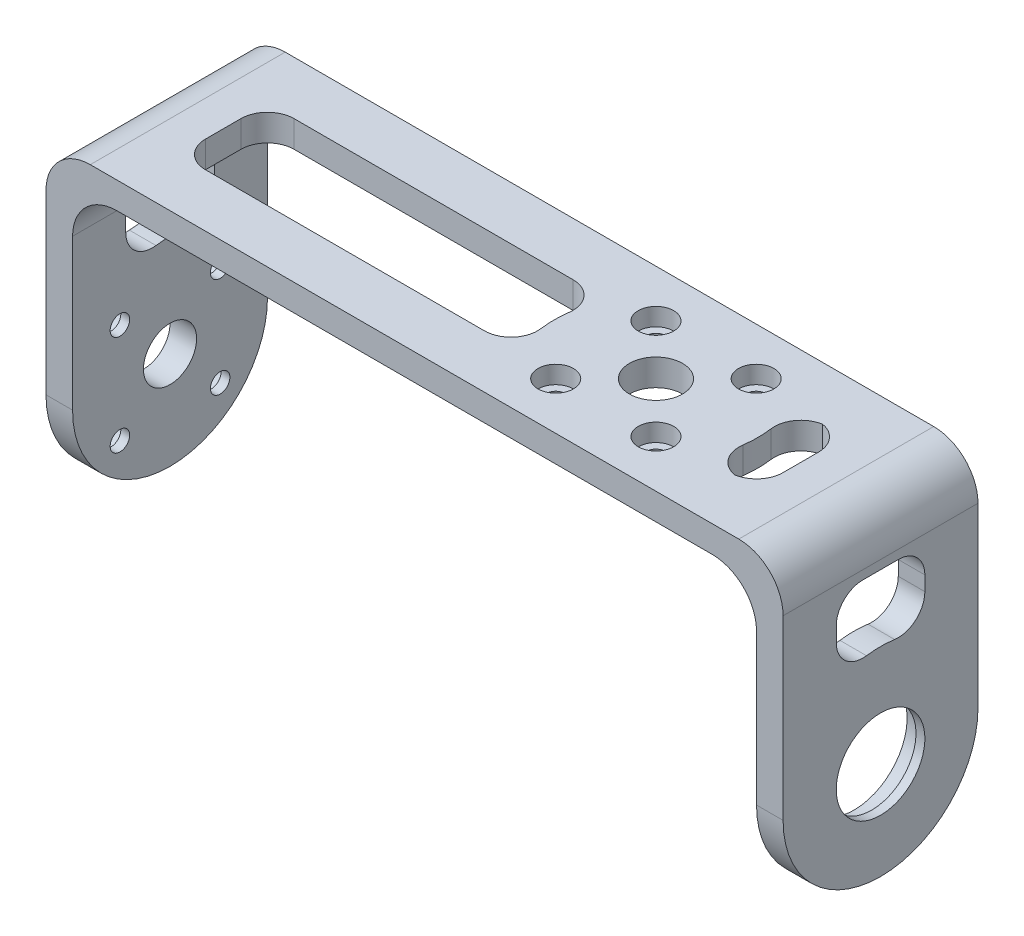
SolidWorks part; units mm, degrees
ref_plane "Front Plane" through (0, 0, 0) normal (0, 0, 1) x (1, 0, 0)
ref_plane "Top Plane" through (0, 0, 0) normal (0, 1, 0) x (1, 0, 0)
ref_plane "Right Plane" through (0, 0, 0) normal (1, 0, 0) x (0, 0, -1)
sketch "Sketch1" plane through (0, 0, 0) normal (0, 1, 0) x (1, 0, 0)
  line L0 (16.25, 0) -> (18.3713, 2.1213) construction
  line L1 (38.6, 11) -> (-38.6, 11)
  line L2 (38.6, 11) -> (38.6, -11)
  line L3 (38.6, -11) -> (-38.6, -11)
  line L4 (-38.6, 11) -> (-38.6, -11)
  line L5 (38.6, 11) -> (-38.6, -11) construction
  line L6 (38.6, -11) -> (-38.6, 11) construction
  line L7 (-38.6, 11) -> (-41.6, 11)
  line L8 (-38.6, 11) -> (-38.6, -11)
  line L9 (-38.6, -11) -> (-41.6, -11)
  line L10 (-41.6, 11) -> (-41.6, -11)
  line L11 (38.6, 11) -> (41.6, 11)
  line L12 (38.6, 11) -> (38.6, -11)
  line L13 (38.6, -11) -> (41.6, -11)
  line L14 (41.6, 11) -> (41.6, -11)
  line L15 (-32.6, 5) -> (-32.6, 11) construction
  line L16 (32.6, 5) -> (26.6062, 5)
  line L17 (32.6, 5) -> (32.6, -5)
  line L18 (32.6, -5) -> (26.6062, -5)
  line L19 (-32.6, 5) -> (-32.6, -5)
  line L20 (32.6, 5) -> (-32.6, -5) construction
  line L21 (32.6, -5) -> (-32.6, 5) construction
  line L22 (-32.6, 5) -> (-38.6, 5) construction
  line L23 (5.8938, 5) -> (-32.6, 5)
  line L24 (5.8938, -5) -> (-32.6, -5)
  circle A0 centre (16.25, 0) radius 3
  arc A1 (5.8938, 5) -> (5.8938, -5) centre (16.25, 0) ccw
  arc A2 (26.6062, -5) -> (26.6062, 5) centre (16.25, 0) ccw
  point P0 (0, 0)
  point P13 (0, 0)
  dimension "D5" = 6
  dimension "D8" = 23
  dimension "D1" = 77.2
  dimension "D2" = 22
  dimension "D3" = 3
  dimension "D4" = 22.35
  dimension "D6" = 45
  dimension "D7" = 6
extrude "Boss-Extrude1" add sketch "Sketch1" against normal blind 3 contours L1 L4 L3 L2 region at (37.7973, 0, 0)
extrude "Boss-Extrude2" add sketch "Sketch1<3>" against normal blind 36 separate body contours L7 L10 L9 L4 | L14 L11 L2 L13 region at (40.1, 0, 0) region at (-40.1, 0, 0)
sketch "Sketch1<3>" plane through (0, 0, 0) normal (0, 1, 0) x (1, 0, 0) same geometry as "Sketch1"
sketch "Sketch2" plane through (-41.6, 0, 0) normal (-1, 0, 0) x (0, 0, 1)
  line L0 (0, -25) -> (5.6569, -19.3431) construction
  line L3 (-11, -36) -> (11, -36) construction
  circle A0 centre (0, -25) radius 3
  circle A1 centre (5.6569, -19.3431) radius 1.1
  dimension "D1" = 6
  dimension "D5" = 2.2
  dimension "D2" = 11
  dimension "D3" = 8
  dimension "D4" = 45
extrude "Cut-Extrude1" cut sketch "Sketch2" against normal up to surface (3 mm away) contours A0 | A1 region at (-41.6, -25, 0) up to face at (-38.6, -18, 0)
sketch "Sketch4" plane through (0, 0, 0) normal (0, 1, 0) x (1, 0, 0)
  line L0 (21.9069, 5.6569) -> (16.25, 0) construction
  line L1 (38.6, 11) -> (-38.6, 11) construction
  circle A0 centre (21.9069, 5.6569) radius 1.1
  dimension "D3" = 2.2
  dimension "D1" = 45
  dimension "D2" = 8
extrude "Cut-Extrude3" cut sketch "Sketch4" against normal up to surface (3 mm away) up to face at (16.25, -3, 3)
pattern_circular "CirPattern2" count 4 over 360 about axis through (16.25, 0, 0) along (0, 1, 0) of "Cut-Extrude3"
sketch "Sketch5" plane through (-41.6, 0, 0) normal (-1, 0, 0) x (0, 0, 1)
  line L0 (-11, -6) -> (-5, -6) construction
  line L2 (-5, -14.6438) -> (-5, -6)
  line L3 (-5, -6) -> (5, -6)
  line L4 (5, -14.6438) -> (5, -6)
  line L5 (-11, -36) -> (-11, 0) construction
  line L6 (-5, -6) -> (-5, 0) construction
  line L7 (55, 0) -> (-55, 0) construction
  line L8 (5, -6) -> (11, -6) construction
  line L9 (11, -36) -> (11, 0) construction
  arc A0 (5, -14.6438) -> (-5, -14.6438) centre (0, -25) ccw
  circle A1 centre (0, -25) radius 3 construction
  dimension "D2" = 23
  dimension "D1" = 6
extrude "Cut-Extrude4" cut sketch "Sketch5" against normal up to surface (83.2 mm away) up to face at (41.6, -18, 0)
sketch "Sketch6" plane through (38.6, 0, 0) normal (-1, 0, 0) x (0, 0, 1)
  circle A0 centre (0, -25) radius 6
  circle A1 centre (0, -25) radius 3 construction
  circle A2 centre (0, -25) radius 5
  dimension "D1" = 12
  dimension "D2" = 10
extrude "Cut-Extrude5" cut sketch "Sketch6" against normal offset from surface (2 mm away) 1 contours A2 | A0 A2 region at (38.6, -25, -5.8303) region at (38.6, -25, 0) up to face at (41.6, -10.036, 0)
extrude "Cut-Extrude6" cut sketch "Sketch6<3>" against normal up to surface (3 mm away) contours A2 region at (38.6, -25, 0) up to face at (41.6, -10.036, 0)
sketch "Sketch6<3>" plane through (38.6, 0, 0) normal (-1, 0, 0) x (0, 0, 1) same geometry as "Sketch6"
combine bodies "Combine1" operation type add bodies to combine 110 108 112
fillet "Fillet2" radius 5 4 edges at (41.6, 0, 0) (-41.6, 0, 0) (38.6, -3, 0) (-38.6, -3, 0)
pattern_circular "CirPattern3" count 4 over 360 about axis through (-30.1147, -25, 0) along (-1, 0, 0) of "Cut-Extrude1" reverse direction yes
fillet "Fillet3" radius 11 4 edges at (40.1, -36, 11) (40.1, -36, -11) (-40.1, -36, -11) (-40.1, -36, 11)
fillet "Fillet4" radius 3 16 edges at (40.1, -14.6438, -5) (40.1, -14.6438, 5) (39.8913, -6, 5) (39.8913, -6, -5) (32.6, -1.5, 5) (26.6062, -1.5, 5) (26.6062, -1.5, -5) (32.6, -1.5, -5) (5.8938, -1.5, 5) (-32.6, -1.5, 5) (-32.6, -1.5, -5) (5.8938, -1.5, -5) (-39.8913, -6, -5) (-39.8913, -6, 5) (-40.1, -14.6438, 5) (-40.1, -14.6438, -5)
sketch "Sketch8" plane through (0, 0, 0) normal (0, 1, 0) x (1, 0, 0)
  circle A0 centre (21.9069, -5.6569) radius 2
  dimension "D1" = 4
extrude "Cut-Extrude7" cut sketch "Sketch8" against normal offset from surface (2 mm away) 1 up to face at (10.5931, -3, -4.5569)
pattern_circular "CirPattern4" count 4 over 360 about axis through (16.25, 0, 0) along (0, 1, 0) of "Cut-Extrude7"
sketch "Sketch9" plane through (-41.6, 0, 0) normal (-1, 0, 0) x (0, 0, 1)
  circle A0 centre (5.6569, -19.3431) radius 2
  dimension "D1" = 4
extrude "Cut-Extrude8" cut sketch "Sketch9" against normal offset from surface (2 mm away) 1 up to face at (-38.6, -19.3431, -4.5569)
pattern_circular "CirPattern5" count 4 over 360 about axis through (-30.1147, -25, 0) along (-1, 0, 0) of "Cut-Extrude8"
move or copy body "Corpo-Mover/Copiar1" [suppressed]
